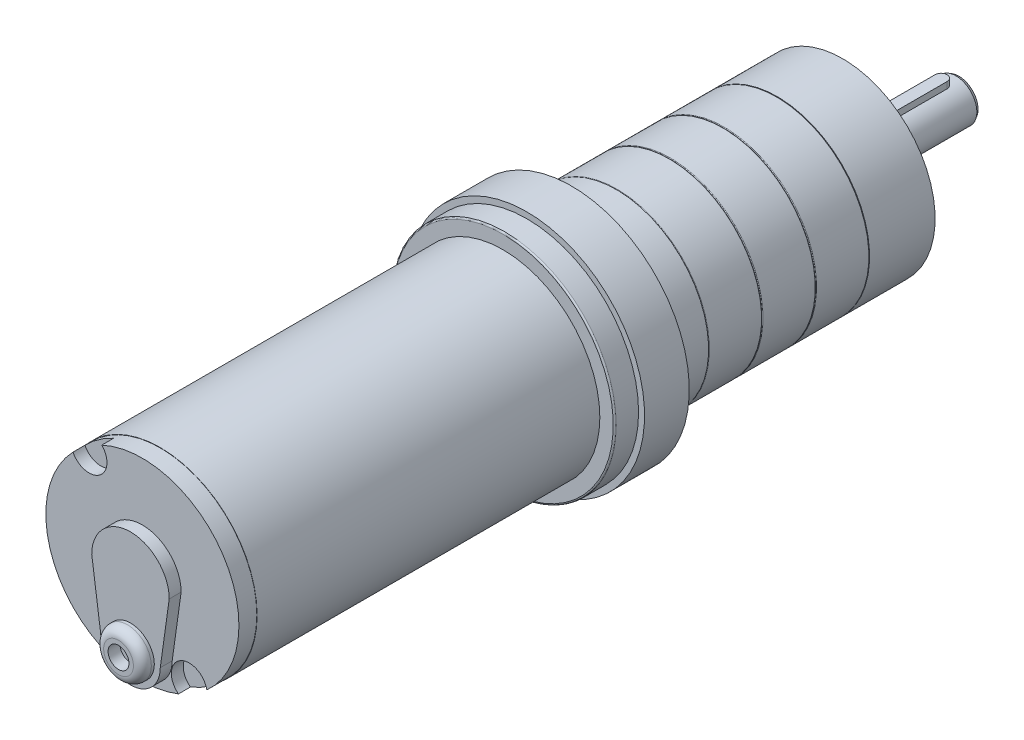
SolidWorks part; units mm, degrees
material "201 Отожженная нержавеющая сталь (SS)"
ref_plane "Спереди" through (0, 0, 0) normal (0, 0, 1) x (1, 0, 0)
ref_plane "Сверху" through (0, 0, 0) normal (0, 1, 0) x (1, 0, 0)
ref_plane "Справа" through (0, 0, 0) normal (1, 0, 0) x (0, 0, -1)
sketch "Эскиз1" plane through (0, 0, 0) normal (0, 0, 1) x (1, 0, 0)
  circle A0 centre (0, 0) radius 32.5
  dimension "D1" = 65
extrude "Вытянуть1" add sketch "Эскиз1" along normal blind 115
sketch "Эскиз2" plane through (0, 0, 115) normal (0, 0, 1) x (1, 0, 0)
  circle A0 centre (0, 0) radius 32.4
  dimension "D1" = 64.8
extrude "Вытянуть2" add sketch "Эскиз2" along normal blind 6
sketch "Эскиз3" plane through (0, 0, 121) normal (0, 0, 1) x (1, 0, 0)
  line L0 (-13, 0) -> (-10, -21.5)
  line L1 (13, 0) -> (10, -21.5)
  arc A0 (13, 0) -> (-13, 0) centre (0, 0) ccw
  arc A1 (-10, -21.5) -> (10, -21.5) centre (0, -21.5) ccw
  circle A3 centre (0, 0) radius 32.4 construction
  dimension "D1" = 13
  dimension "D2" = 10
  dimension "D3" = 21.5
extrude "Вытянуть3" add sketch "Эскиз3" along normal blind 4
sketch "Эскиз5" plane through (0, 0, 125) normal (0, 0, 1) x (1, 0, 0)
  circle A0 centre (0, -21.5) radius 8
  dimension "D1" = 16
extrude "Вытянуть4" add sketch "Эскиз5" along normal blind 4
fillet "Скругление1" radius 3 1 edges at (8, -21.5, 129)
sketch "Эскиз6" plane through (0, 0, 125) normal (0, 0, 1) x (1, 0, 0)
  circle A0 centre (0, -21.5) radius 3.5
  dimension "D1" = 7
extrude "Вытянуть5" cut sketch "Эскиз6" along normal blind 14
sketch "Эскиз7" plane through (0, 0, 121) normal (0, 0, 1) x (1, 0, 0)
  circle A0 centre (15.7181, -25.2535) radius 6
  circle A1 centre (-17.8952, 25.1664) radius 6
  dimension "D1" = 12
  dimension "D2" = 2.7181
  dimension "D3" = 30.8952
  dimension "D4" = 25.1664
  dimension "D5" = 25.2535
extrude "Вытянуть6" cut sketch "Эскиз7" against normal blind 4
sketch "Эскиз8" plane through (0, 0, 0) normal (0, 0, -1) x (-1, 0, 0)
  circle A0 centre (0, 0) radius 37.5
  dimension "D1" = 75
extrude "Вытянуть7" add sketch "Эскиз8" along normal blind 8
fillet "Скругление4" radius 0.5 1 edges at (-37.5, 0, 0)
sketch "Эскиз9" plane through (0, 0, -8) normal (0, 0, -1) x (-1, 0, 0)
  circle A0 centre (0, 0) radius 39.5
  dimension "D1" = 79
extrude "Вытянуть8" add sketch "Эскиз9" along normal blind 15
sketch "Эскиз10" plane through (0, 0, -23) normal (0, 0, -1) x (-1, 0, 0)
  circle A0 centre (0, 0) radius 31
  dimension "D1" = 62
extrude "Вытянуть9" add sketch "Эскиз10" along normal blind 15
sketch "Эскиз13" plane through (0, 0, -38) normal (0, 0, -1) x (-1, 0, 0)
  circle A0 centre (0, 0) radius 31
  dimension "D1" = 62
extrude "Вытянуть12" add sketch "Эскиз13" along normal blind 18 separate body
sketch "Эскиз14" plane through (0, 0, -56) normal (0, 0, -1) x (-1, 0, 0)
  circle A0 centre (0, 0) radius 31
  dimension "D1" = 62
extrude "Вытянуть14" add sketch "Эскиз14" along normal blind 18 separate body
fillet "Скругление5" radius 0.25 1 edges at (-31, 0, -38)
fillet "Скругление7" radius 0.25 1 edges at (-31, 0, -56)
fillet "Скругление8" radius 0.25 1 edges at (-31, 0, -56)
sketch "Эскиз15" plane through (0, 0, -74) normal (0, 0, -1) x (-1, 0, 0)
  circle A0 centre (0, 0) radius 31
  dimension "D1" = 62
extrude "Вытянуть16" add sketch "Эскиз15" along normal blind 18 separate body
fillet "Скругление9" radius 0.25 1 edges at (-31, 0, -74)
fillet "Скругление10" radius 0.25 1 edges at (-31, 0, -74)
sketch "Эскиз16" plane through (0, 0, -92) normal (0, 0, -1) x (-1, 0, 0)
  circle A0 centre (0, 0) radius 31
  dimension "D1" = 62
extrude "Вытянуть18" add sketch "Эскиз16" along normal blind 22 separate body
fillet "Скругление11" radius 0.25 1 edges at (-31, 0, -92)
sketch "Эскиз17" plane through (0, 0, -114) normal (0, 0, -1) x (-1, 0, 0)
  circle A0 centre (0, 0) radius 20
  dimension "D1" = 40
extrude "Вытянуть19" add sketch "Эскиз17" along normal blind 5 separate body
sketch "Эскиз18" plane through (0, 0, -119) normal (0, 0, -1) x (-1, 0, 0)
  circle A0 centre (0, 0) radius 7.5
  dimension "D1" = 15
extrude "Вытянуть20" add sketch "Эскиз18" along normal blind 4 separate body
sketch "Эскиз19" plane through (0, 0, -123) normal (0, 0, -1) x (-1, 0, 0)
  circle A0 centre (0, 0) radius 7
  dimension "D1" = 14
extrude "Вытянуть21" add sketch "Эскиз19" along normal blind 30 separate body
chamfer "Фаска1" distance 1 angle 31 1 edges at (-7, 0, -153)
sketch "Эскиз20" plane through (0, 0, 0) normal (0, 1, 0) x (1, 0, 0)
  line L3 (-2, 147) -> (-2, 130)
  line L4 (2, 147) -> (2, 130)
  arc A0 (2, 147) -> (-2, 147) centre (0, 147) ccw
  arc A1 (-2, 130) -> (2, 130) centre (0, 130) ccw
  dimension "D1" = 2
  dimension "D2" = 130
  dimension "D3" = 147
sketch "Эскиз21" plane through (0, 0, -114) normal (0, 0, -1) x (-1, 0, 0)
  line L0 (1.5754, 0) -> (57.2986, 0) construction
  line L1 (0, 0) -> (0, 42.3348) construction
  line L2 (-31, 0) -> (-31, 29.5285) construction
  circle A0 centre (0, 26.5) radius 2.5
  circle A1 centre (0, -26.5) radius 2.5
  circle A2 centre (-26.5, 0) radius 2.5
  circle A3 centre (26.5, 0) radius 2.5
  circle A5 centre (0, 0) radius 31 construction
  dimension "D1" = 53
  dimension "D2" = 4.5
  dimension "D3" = 5
  dimension "D4" = 26.5
extrude "Вытянуть23" cut sketch "Эскиз21" against normal blind 16.5
extrude "Вытянуть27" add sketch "Эскиз20" along normal blind 2.85 from offset 6
sketch "Эскиз22" plane through (0, 0, 0) normal (0, 1, 0) x (1, 0, 0)
  line L0 (0, 153) -> (0, 164.4717) construction
